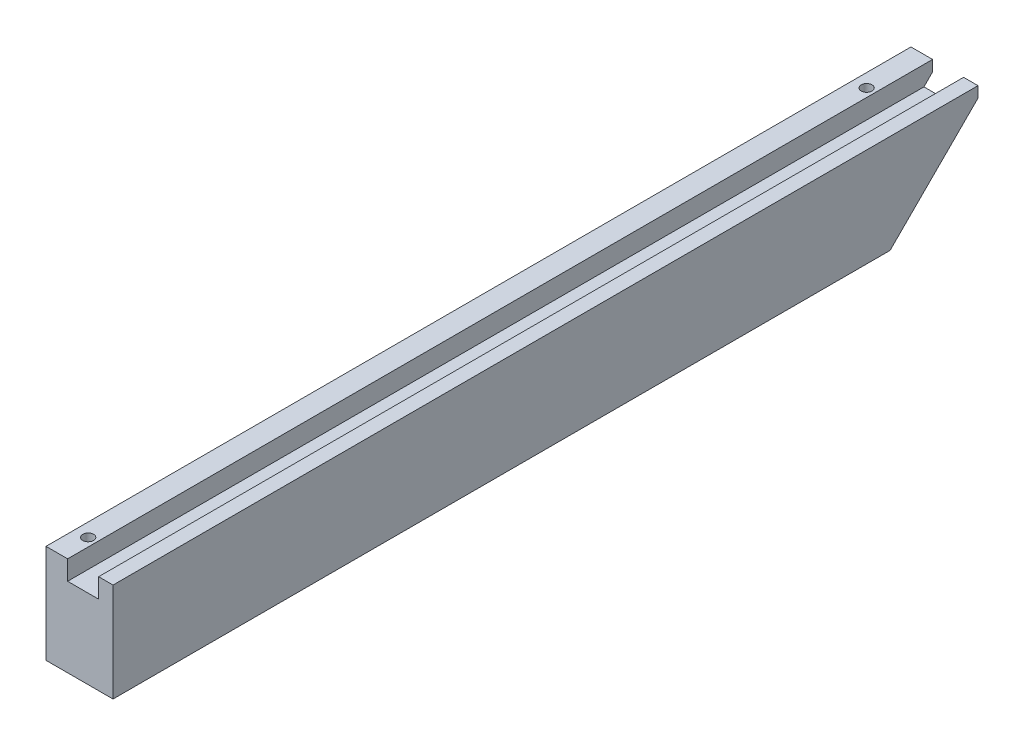
SolidWorks part; units mm, degrees
ref_plane "Front Plane" through (0, 0, 0) normal (0, 0, 1) x (1, 0, 0)
ref_plane "Top Plane" through (0, 0, 0) normal (0, 1, 0) x (1, 0, 0)
ref_plane "Right Plane" through (0, 0, 0) normal (1, 0, 0) x (0, 0, -1)
ref_axis "X-Axis" through (0, 0, 0) along (1, 0, 0)
ref_axis "Y-Axis" through (0, 42.2917, 0) along (0, -1, 0)
ref_axis "Z-Axis" through (0, 0, 55.0015) along (0, 0, -1)
sketch "Sketch1" plane through (0, 0, 0) normal (0, 0, 1) x (1, 0, 0)
  line L0 (7.9911, 6.2786) -> (10.9911, 6.2786)
  line L1 (10.9911, 6.2786) -> (10.9911, 3.5786)
  line L2 (10.9911, 3.5786) -> (15.2911, 3.5786)
  line L3 (15.2911, 3.5786) -> (15.2911, 6.2786)
  line L4 (15.2911, 6.2786) -> (17.2911, 6.2786)
  line L5 (17.2911, 6.2786) -> (17.2911, -7.4214)
  line L6 (17.2911, -7.4214) -> (7.9911, -7.4214)
  line L7 (7.9911, -7.4214) -> (7.9911, 6.2786)
  line L8 (-0.8459, -4.4214) -> (52.4677, -4.4214) construction
  line L9 (52.4677, -4.4214) -> (52.4677, 5.5786) construction
  line L10 (52.4677, 5.5786) -> (-1.8799, 5.5786) construction
  dimension "D1" = 3
  dimension "D2" = 2
  dimension "D3" = 4.3
  dimension "D4" = 11
  dimension "D5" = 13.7
  dimension "Largeur_Rail" = 9.3
  dimension "Profondeur_Rail" = 2.7
extrude "Rail-Extrude" add sketch "Sketch1" along normal blind 120
sketch "Sketch2" plane through (0, 6.2786, 0) normal (0, 1, 0) x (1, 0, 0)
  line L0 (9.8411, 0) -> (9.8411, -8) construction
  line L1 (10.9911, 0) -> (7.9911, 0) construction
  line L2 (7.9911, -120) -> (7.9911, 0) construction
  circle A0 centre (9.8411, -8) radius 0.75
  dimension "D1" = 1.5
  dimension "D2" = 8
  dimension "D3" = 1.85
extrude "First Hole" cut sketch "Sketch2" against normal through all
sketch "Sketch3" plane through (0, 6.2786, 0) normal (0, 1, 0) x (1, 0, 0)
  line L0 (9.8411, -8) -> (9.8411, -116) construction
  circle A0 centre (9.8411, -116) radius 0.75
  circle A1 centre (9.8411, -8) radius 0.75 construction
  dimension "D1" = 108
extrude "Last Hole" cut sketch "Sketch3" against normal through all
sketch "Sketch5" plane through (7.9911, 0, 0) normal (-1, 0, 0) x (0, 0, 1)
  line L5 (120, 6.2786) -> (0, 6.2786) construction
  line L6 (120, -7.4214) -> (0, -7.4214) construction
  line L7 (0, -5.4214) -> (10, -5.4214) construction
  line L8 (0, -5.4214) -> (0, -7.4214) construction
  line L9 (0, -7.4214) -> (10, -7.4214) construction
  line L10 (10, -5.4214) -> (10, -7.4214) construction
  line L11 (0, 6.2786) -> (0, -7.4214) construction
  line L12 (12.2, -7.4214) -> (0, 4.7786)
  line L13 (0, 4.7786) -> (0, -7.4214)
  line L14 (0, -7.4214) -> (12.2, -7.4214)
  dimension "D1" = 2
  dimension "D2" = 10
  dimension "D3" = 45
  dimension "D4" = 1.5
extrude "Angle" cut sketch "Sketch5" against normal through all
equation "\"Largeur Bande\"= 8.3"
equation "\"Largeur_Rail\"= \"Largeur Bande\" + 1"
equation "\"Profondeur Bande\"= 2.5"
equation "\"Profondeur_Rail\" = \"Profondeur Bande\" + 0.2"
equation "\"Largeur Feeder\"= \"Largeur Rail\" + 1.2 + 1.2 + 0.3"
equation "\"Largeur Rail\"= \"Largeur Bande\" + 1"
equation "\"D1@Boss-Extrude1\"=\"Largeur Feeder\"/2"
equation "\"D2@Boss-Extrude1\"=\"Largeur Feeder\"/2"
